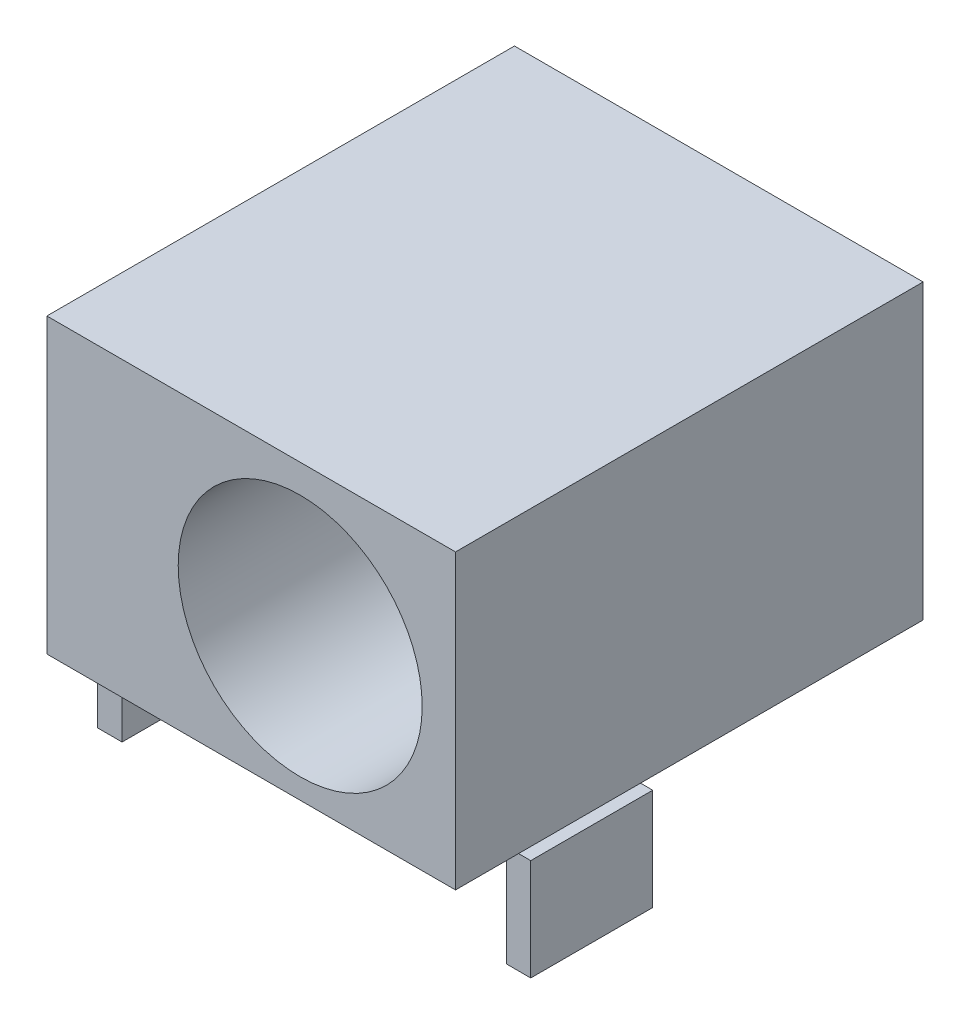
SolidWorks part; units mm, degrees
ref_plane "Front Plane" through (0, 0, 0) normal (0, 0, 1) x (1, 0, 0)
ref_plane "Top Plane" through (0, 0, 0) normal (0, 1, 0) x (1, 0, 0)
ref_plane "Right Plane" through (0, 0, 0) normal (1, 0, 0) x (0, 0, -1)
sketch "Sketch1" plane through (0, 0, 0) normal (0, 1, 0) x (1, 0, 0)
  line L0 (0, 5.75) -> (0, -5.75) construction
  line L1 (-5.025, 5.75) -> (5.025, 5.75)
  line L2 (-5.025, 5.75) -> (-5.025, -5.75)
  line L3 (-5.025, -5.75) -> (5.025, -5.75)
  line L4 (5.025, 5.75) -> (5.025, -5.75)
  line L5 (4.725, -1.2) -> (5.325, -1.2)
  line L6 (4.725, -1.2) -> (4.725, -4.2)
  line L7 (4.725, -4.2) -> (5.325, -4.2)
  line L8 (5.325, -1.2) -> (5.325, -4.2)
  line L9 (-4.725, -4.2) -> (-5.325, -4.2)
  line L10 (-4.725, -1.2) -> (-4.725, -4.2)
  line L11 (-5.325, -1.2) -> (-5.325, -4.2)
  line L12 (-4.725, -1.2) -> (-5.325, -1.2)
  point P4 (0, 5.75)
  point P6 (5.025, 0)
  point P11 (5.325, -2.7)
  point P12 (5.025, -1.2)
  dimension "D1" = 11.5
  dimension "D2" = 10.05
  dimension "D3" = 0.6
  dimension "D4" = 3
  dimension "D5" = 3.05
extrude "Boss-Extrude1" add sketch "Sketch1" against normal blind 2.5 contours L2 L12 L11 L9 | L10 L12 L2 L9 | L6 L7 L4 L5 | L8 L5 L4 L7 region at (-4.875, 0, 2.7) region at (-5.175, 0, 2.7) region at (5.175, 0, 2.7) region at (4.875, 0, 2.7)
extrude "Boss-Extrude2" add sketch "Sketch1<3>" along normal blind 7.2 contours L1 L0 L3 L4 L7 L6 L5 | L0 L1 L2 L12 L10 L9 L3 | L6 L7 L4 L5 | L10 L12 L2 L9 region at (2.4751, 0, -0.0427) region at (-2.4751, 0, -0.0427) region at (-4.875, 0, 2.7) region at (4.875, 0, 2.7)
sketch "Sketch1<3>" plane through (0, 0, 0) normal (0, 1, 0) x (1, 0, 0) same geometry as "Sketch1"
sketch3d "3DSketch2"
  line L0 (-5.025, 7.2, 5.75) -> (-5.025, 0, 5.75) construction
  line L1 (-5.025, 0, 5.75) -> (5.025, 0, 5.75) construction
  circle A0 centre (1.205, 3.5, 5.75) radius 3
  point P2 (1.205, 3.5, 8.75)
  point P3 (1.1663, 3.728, 5.75)
  dimension "D1" = 6
  dimension "D2" = 6.23
  dimension "D3" = 3.5
extrude "Cut-Extrude1" cut sketch "3DSketch2" along direction (0, 0, -1) on the side of the normal blind 8.2
